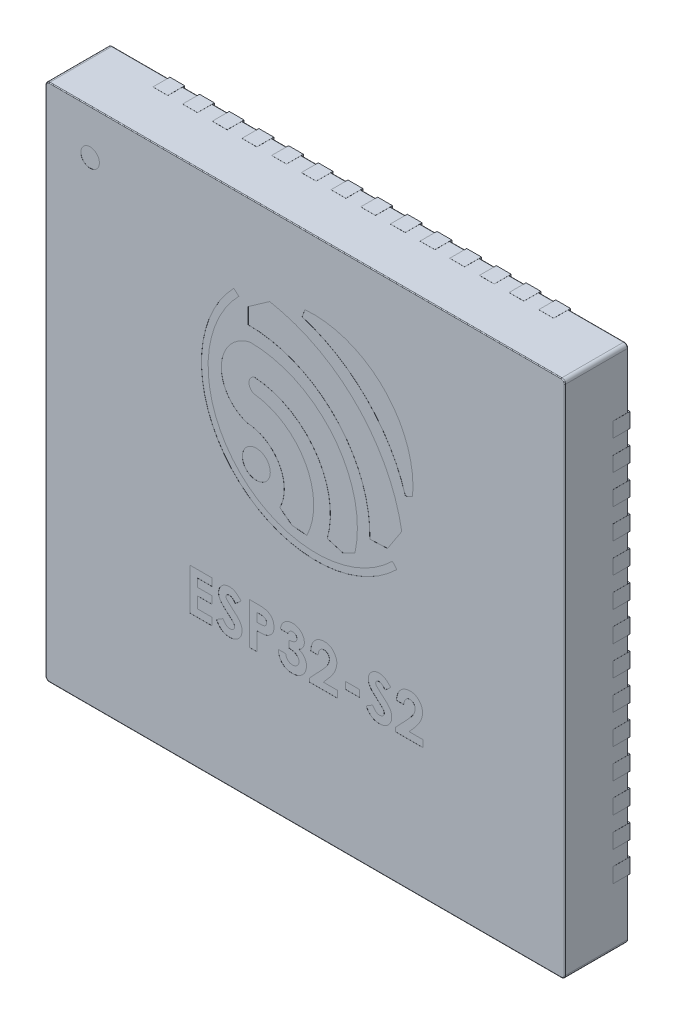
SolidWorks part; units mm, degrees
other "ESP32-S2-SoC" parameters "D5"=0.3678, "D1"=3.1308, "D2"=3.0402, "D3"=0.4115, "D4"=0.3, "D6"=0.3296, "D7"=0.2637, "D8"=0.9806, "D10"=0.4, "D11"=0.25, "D9"=7
ref_plane "Front Plane" through (0, 0, 0) normal (0, 0, 1) x (1, 0, 0)
ref_plane "Top Plane" through (0, 0, 0) normal (0, 1, 0) x (1, 0, 0)
ref_plane "Right Plane" through (0, 0, 0) normal (1, 0, 0) x (0, 0, -1)
sketch "Sketch1" plane through (0, 0, 0) normal (0, 1, 0) x (1, 0, 0)
  line L1 (-3.5, -3.5) -> (3.5, -3.5)
  line L2 (-3.5, -3.5) -> (-3.5, 3.5)
  line L3 (-3.5, 3.5) -> (3.5, 3.5)
  line L4 (3.5, -3.5) -> (3.5, 3.5)
  line L5 (-3.5, -3.5) -> (3.5, 3.5) construction
  line L6 (-3.5, 3.5) -> (3.5, -3.5) construction
  point P0 (0, 0)
  dimension "D1" = 7
  dimension "D2" = 7
extrude "Boss-Extrude1" add sketch "Sketch1" along normal blind 0.85
fillet "Fillet1" radius 0.05 4 edges at (3.5, 0.425, -3.5) (3.5, 0.425, 3.5) (-3.5, 0.425, 3.5) (-3.5, 0.425, -3.5)
fillet "Fillet2" radius 0.01 16 edges at (3.4854, 0.85, 3.4854) (0, 0.85, 3.5) (-3.4854, 0.85, 3.4854) (-3.5, 0.85, 0) (-3.4854, 0.85, -3.4854) (0, 0.85, -3.5) (3.4854, 0.85, -3.4854) (3.5, 0.85, 0) (3.5, 0, 0) (3.4854, 0, -3.4854) (0, 0, -3.5) (3.4854, 0, 3.4854) (0, 0, 3.5) (-3.4854, 0, 3.4854) (-3.5, 0, 0) (-3.4854, 0, -3.4854)
sketch "Sketch2" plane through (0, 0, 0) normal (0, -1, 0) x (1, 0, 0)
  line L0 (1.5, 2) -> (2, 1.5)
  line L1 (-1.875, -2) -> (1.875, -2)
  line L2 (-2, -1.875) -> (-2, 1.875)
  line L3 (-1.875, 2) -> (1.5, 2)
  line L4 (2, -1.875) -> (2, 1.5)
  line L5 (-1.9634, -1.9634) -> (2, 2) construction
  line L6 (-1.9634, 1.9634) -> (1.9634, -1.9634) construction
  line L7 (1.5, 2) -> (2, 2) construction
  line L8 (2, 1.5) -> (2, 2) construction
  line L9 (-2, 2) -> (-1.875, 2) construction
  line L10 (-2, 2) -> (-1.9634, 1.9634) construction
  line L11 (-2, 1.875) -> (-2, 2) construction
  line L12 (-2, -2) -> (-2, -1.875) construction
  line L13 (-2, -2) -> (-1.9634, -1.9634) construction
  line L14 (-2, -2) -> (-1.875, -2) construction
  line L15 (2, -2) -> (2, -1.875) construction
  line L16 (1.9634, -1.9634) -> (2, -2) construction
  line L17 (1.875, -2) -> (2, -2) construction
  line L18 (-1.9, 3.501) -> (-1.9, 3.101)
  line L23 (-0.3, 3.501) -> (-0.1, 3.501)
  line L24 (-0.3, 3.501) -> (-0.3, 3.101)
  line L25 (-0.3, 3.101) -> (-0.1, 3.101)
  line L26 (-0.1, 3.501) -> (-0.1, 3.101)
  line L27 (-0.3, 3.501) -> (-0.1, 3.101) construction
  line L28 (-0.3, 3.101) -> (-0.1, 3.501) construction
  line L30 (-0.7, 3.501) -> (-0.7, 3.101)
  line L31 (-0.7, 3.501) -> (-0.5, 3.501)
  line L32 (-0.5, 3.501) -> (-0.5, 3.101)
  line L33 (-0.7, 3.101) -> (-0.5, 3.101)
  line L34 (-0.7, 3.101) -> (-0.5, 3.501) construction
  line L35 (-0.7, 3.501) -> (-0.5, 3.101) construction
  line L36 (-1.1, 3.501) -> (-1.1, 3.101)
  line L37 (-1.1, 3.501) -> (-0.9, 3.501)
  line L38 (-0.9, 3.501) -> (-0.9, 3.101)
  line L39 (-1.1, 3.101) -> (-0.9, 3.101)
  line L40 (-1.1, 3.101) -> (-0.9, 3.501) construction
  line L41 (-1.1, 3.501) -> (-0.9, 3.101) construction
  line L42 (-1.5, 3.501) -> (-1.5, 3.101)
  line L43 (-1.5, 3.501) -> (-1.3, 3.501)
  line L44 (-1.3, 3.501) -> (-1.3, 3.101)
  line L45 (-1.5, 3.101) -> (-1.3, 3.101)
  line L46 (-1.5, 3.101) -> (-1.3, 3.501) construction
  line L47 (-1.5, 3.501) -> (-1.3, 3.101) construction
  line L48 (-0.3, 3.501) -> (-0.7, 3.501) construction
  line L49 (0, 0.0183) -> (0, 4.8642) construction
  line L66 (0, -1000) -> (0, 49000) construction
  line L162 (-1.9, 3.501) -> (-1.7, 3.501)
  line L163 (-3.5, 3.5) -> (3.5, 3.5) construction
  line L164 (-1.7, 3.501) -> (-1.7, 3.101)
  line L165 (-1.9, 3.101) -> (-1.7, 3.101)
  line L166 (-1.9, 3.101) -> (-1.7, 3.501) construction
  line L167 (-1.9, 3.501) -> (-1.7, 3.101) construction
  line L168 (-2.3, 3.501) -> (-2.3, 3.101)
  line L169 (-2.3, 3.501) -> (-2.1, 3.501)
  line L170 (-2.1, 3.501) -> (-2.1, 3.101)
  line L171 (-2.3, 3.101) -> (-2.1, 3.101)
  line L172 (-2.3, 3.101) -> (-2.1, 3.501) construction
  line L173 (-2.3, 3.501) -> (-2.1, 3.101) construction
  line L174 (-2.7, 3.501) -> (-2.7, 3.101)
  line L175 (-2.7, 3.501) -> (-2.5, 3.501)
  line L176 (-2.5, 3.501) -> (-2.5, 3.101)
  line L177 (-2.7, 3.101) -> (-2.5, 3.101)
  line L178 (-2.7, 3.101) -> (-2.5, 3.501) construction
  line L179 (-2.7, 3.501) -> (-2.5, 3.101) construction
  line L180 (-1000, 0) -> (49000, 0) construction
  line L181 (2.7, 3.501) -> (2.5, 3.101) construction
  line L182 (2.7, 3.101) -> (2.5, 3.501) construction
  line L183 (2.3, 3.501) -> (2.1, 3.101) construction
  line L184 (2.3, 3.101) -> (2.1, 3.501) construction
  line L185 (1.9, 3.501) -> (1.7, 3.101) construction
  line L186 (1.9, 3.101) -> (1.7, 3.501) construction
  line L187 (0.3, 3.501) -> (0.7, 3.501) construction
  line L188 (1.5, 3.501) -> (1.3, 3.101) construction
  line L189 (1.5, 3.101) -> (1.3, 3.501) construction
  line L190 (1.1, 3.501) -> (0.9, 3.101) construction
  line L191 (1.1, 3.101) -> (0.9, 3.501) construction
  line L192 (0.7, 3.501) -> (0.5, 3.101) construction
  line L193 (0.7, 3.101) -> (0.5, 3.501) construction
  line L194 (0.3, 3.101) -> (0.1, 3.501) construction
  line L195 (0.3, 3.501) -> (0.1, 3.101) construction
  line L196 (2.7, 3.101) -> (2.5, 3.101)
  line L197 (2.5, 3.501) -> (2.5, 3.101)
  line L198 (2.7, 3.501) -> (2.5, 3.501)
  line L199 (2.7, 3.501) -> (2.7, 3.101)
  line L200 (2.3, 3.101) -> (2.1, 3.101)
  line L201 (2.1, 3.501) -> (2.1, 3.101)
  line L202 (2.3, 3.501) -> (2.1, 3.501)
  line L203 (2.3, 3.501) -> (2.3, 3.101)
  line L204 (1.9, 3.101) -> (1.7, 3.101)
  line L205 (1.7, 3.501) -> (1.7, 3.101)
  line L206 (1.9, 3.501) -> (1.7, 3.501)
  line L207 (1.5, 3.101) -> (1.3, 3.101)
  line L208 (1.3, 3.501) -> (1.3, 3.101)
  line L209 (1.5, 3.501) -> (1.3, 3.501)
  line L210 (1.5, 3.501) -> (1.5, 3.101)
  line L211 (1.1, 3.101) -> (0.9, 3.101)
  line L212 (0.9, 3.501) -> (0.9, 3.101)
  line L213 (1.1, 3.501) -> (0.9, 3.501)
  line L214 (1.1, 3.501) -> (1.1, 3.101)
  line L215 (0.7, 3.101) -> (0.5, 3.101)
  line L216 (0.5, 3.501) -> (0.5, 3.101)
  line L217 (0.7, 3.501) -> (0.5, 3.501)
  line L218 (0.7, 3.501) -> (0.7, 3.101)
  line L219 (0.1, 3.501) -> (0.1, 3.101)
  line L220 (0.3, 3.101) -> (0.1, 3.101)
  line L221 (0.3, 3.501) -> (0.3, 3.101)
  line L222 (0.3, 3.501) -> (0.1, 3.501)
  line L223 (1.9, 3.501) -> (1.9, 3.101)
  line L224 (0.3, -3.501) -> (0.1, -3.101) construction
  line L225 (0.3, -3.101) -> (0.1, -3.501) construction
  line L226 (0.7, -3.101) -> (0.5, -3.501) construction
  line L227 (0.7, -3.501) -> (0.5, -3.101) construction
  line L228 (1.1, -3.101) -> (0.9, -3.501) construction
  line L229 (1.1, -3.501) -> (0.9, -3.101) construction
  line L230 (1.5, -3.101) -> (1.3, -3.501) construction
  line L231 (1.5, -3.501) -> (1.3, -3.101) construction
  line L232 (0.3, -3.501) -> (0.7, -3.501) construction
  line L233 (1.9, -3.101) -> (1.7, -3.501) construction
  line L234 (1.9, -3.501) -> (1.7, -3.101) construction
  line L235 (2.3, -3.101) -> (2.1, -3.501) construction
  line L236 (2.3, -3.501) -> (2.1, -3.101) construction
  line L237 (2.7, -3.101) -> (2.5, -3.501) construction
  line L238 (2.7, -3.501) -> (2.5, -3.101) construction
  line L239 (-2.7, -3.501) -> (-2.5, -3.101) construction
  line L240 (-2.7, -3.101) -> (-2.5, -3.501) construction
  line L241 (-2.3, -3.501) -> (-2.1, -3.101) construction
  line L242 (-2.3, -3.101) -> (-2.1, -3.501) construction
  line L243 (-1.9, -3.501) -> (-1.7, -3.101) construction
  line L244 (-1.9, -3.101) -> (-1.7, -3.501) construction
  line L245 (-0.3, -3.501) -> (-0.7, -3.501) construction
  line L246 (-1.5, -3.501) -> (-1.3, -3.101) construction
  line L247 (-1.5, -3.101) -> (-1.3, -3.501) construction
  line L248 (-1.1, -3.501) -> (-0.9, -3.101) construction
  line L249 (-1.1, -3.101) -> (-0.9, -3.501) construction
  line L250 (-0.7, -3.501) -> (-0.5, -3.101) construction
  line L251 (-0.7, -3.101) -> (-0.5, -3.501) construction
  line L252 (-0.3, -3.101) -> (-0.1, -3.501) construction
  line L253 (-0.3, -3.501) -> (-0.1, -3.101) construction
  line L254 (1.9, -3.501) -> (1.9, -3.101)
  line L255 (0.3, -3.501) -> (0.1, -3.501)
  line L256 (0.3, -3.501) -> (0.3, -3.101)
  line L257 (0.3, -3.101) -> (0.1, -3.101)
  line L258 (0.1, -3.501) -> (0.1, -3.101)
  line L259 (0.7, -3.501) -> (0.7, -3.101)
  line L260 (0.7, -3.501) -> (0.5, -3.501)
  line L261 (0.5, -3.501) -> (0.5, -3.101)
  line L262 (0.7, -3.101) -> (0.5, -3.101)
  line L263 (1.1, -3.501) -> (1.1, -3.101)
  line L264 (1.1, -3.501) -> (0.9, -3.501)
  line L265 (0.9, -3.501) -> (0.9, -3.101)
  line L266 (1.1, -3.101) -> (0.9, -3.101)
  line L267 (1.5, -3.501) -> (1.5, -3.101)
  line L268 (1.5, -3.501) -> (1.3, -3.501)
  line L269 (1.3, -3.501) -> (1.3, -3.101)
  line L270 (1.5, -3.101) -> (1.3, -3.101)
  line L271 (1.9, -3.501) -> (1.7, -3.501)
  line L272 (1.7, -3.501) -> (1.7, -3.101)
  line L273 (1.9, -3.101) -> (1.7, -3.101)
  line L274 (2.3, -3.501) -> (2.3, -3.101)
  line L275 (2.3, -3.501) -> (2.1, -3.501)
  line L276 (2.1, -3.501) -> (2.1, -3.101)
  line L277 (2.3, -3.101) -> (2.1, -3.101)
  line L278 (2.7, -3.501) -> (2.7, -3.101)
  line L279 (2.7, -3.501) -> (2.5, -3.501)
  line L280 (2.5, -3.501) -> (2.5, -3.101)
  line L281 (2.7, -3.101) -> (2.5, -3.101)
  line L282 (-2.7, -3.101) -> (-2.5, -3.101)
  line L283 (-2.5, -3.501) -> (-2.5, -3.101)
  line L284 (-2.7, -3.501) -> (-2.5, -3.501)
  line L285 (-2.7, -3.501) -> (-2.7, -3.101)
  line L286 (-2.3, -3.101) -> (-2.1, -3.101)
  line L287 (-2.1, -3.501) -> (-2.1, -3.101)
  line L288 (-2.3, -3.501) -> (-2.1, -3.501)
  line L289 (-2.3, -3.501) -> (-2.3, -3.101)
  line L290 (-1.9, -3.101) -> (-1.7, -3.101)
  line L291 (-1.7, -3.501) -> (-1.7, -3.101)
  line L292 (-1.9, -3.501) -> (-1.7, -3.501)
  line L293 (-1.5, -3.101) -> (-1.3, -3.101)
  line L294 (-1.3, -3.501) -> (-1.3, -3.101)
  line L295 (-1.5, -3.501) -> (-1.3, -3.501)
  line L296 (-1.5, -3.501) -> (-1.5, -3.101)
  line L297 (-1.1, -3.101) -> (-0.9, -3.101)
  line L298 (-0.9, -3.501) -> (-0.9, -3.101)
  line L299 (-1.1, -3.501) -> (-0.9, -3.501)
  line L300 (-1.1, -3.501) -> (-1.1, -3.101)
  line L301 (-0.7, -3.101) -> (-0.5, -3.101)
  line L302 (-0.5, -3.501) -> (-0.5, -3.101)
  line L303 (-0.7, -3.501) -> (-0.5, -3.501)
  line L304 (-0.7, -3.501) -> (-0.7, -3.101)
  line L305 (-0.1, -3.501) -> (-0.1, -3.101)
  line L306 (-0.3, -3.101) -> (-0.1, -3.101)
  line L307 (-0.3, -3.501) -> (-0.3, -3.101)
  line L308 (-0.3, -3.501) -> (-0.1, -3.501)
  line L309 (-1.9, -3.501) -> (-1.9, -3.101)
  line L310 (3.501, 0.3) -> (3.101, 0.1) construction
  line L311 (3.101, 0.3) -> (3.501, 0.1) construction
  line L312 (3.101, 0.7) -> (3.501, 0.5) construction
  line L313 (3.501, 0.7) -> (3.101, 0.5) construction
  line L314 (3.101, 1.1) -> (3.501, 0.9) construction
  line L315 (3.501, 1.1) -> (3.101, 0.9) construction
  line L316 (3.101, 1.5) -> (3.501, 1.3) construction
  line L317 (3.501, 1.5) -> (3.101, 1.3) construction
  line L318 (3.501, 0.3) -> (3.501, 0.7) construction
  line L319 (3.101, 1.9) -> (3.501, 1.7) construction
  line L320 (3.501, 1.9) -> (3.101, 1.7) construction
  line L321 (3.101, 2.3) -> (3.501, 2.1) construction
  line L322 (3.501, 2.3) -> (3.101, 2.1) construction
  line L323 (3.101, 2.7) -> (3.501, 2.5) construction
  line L324 (3.501, 2.7) -> (3.101, 2.5) construction
  line L325 (3.501, -2.7) -> (3.101, -2.5) construction
  line L326 (3.101, -2.7) -> (3.501, -2.5) construction
  line L327 (3.501, -2.3) -> (3.101, -2.1) construction
  line L328 (3.101, -2.3) -> (3.501, -2.1) construction
  line L329 (3.501, -1.9) -> (3.101, -1.7) construction
  line L330 (3.101, -1.9) -> (3.501, -1.7) construction
  line L331 (3.501, -0.3) -> (3.501, -0.7) construction
  line L332 (3.501, -1.5) -> (3.101, -1.3) construction
  line L333 (3.101, -1.5) -> (3.501, -1.3) construction
  line L334 (3.501, -1.1) -> (3.101, -0.9) construction
  line L335 (3.101, -1.1) -> (3.501, -0.9) construction
  line L336 (3.501, -0.7) -> (3.101, -0.5) construction
  line L337 (3.101, -0.7) -> (3.501, -0.5) construction
  line L338 (3.101, -0.3) -> (3.501, -0.1) construction
  line L339 (3.501, -0.3) -> (3.101, -0.1) construction
  line L340 (3.501, 1.9) -> (3.101, 1.9)
  line L341 (3.501, 0.3) -> (3.501, 0.1)
  line L342 (3.501, 0.3) -> (3.101, 0.3)
  line L343 (3.101, 0.3) -> (3.101, 0.1)
  line L344 (3.501, 0.1) -> (3.101, 0.1)
  line L345 (3.501, 0.7) -> (3.101, 0.7)
  line L346 (3.501, 0.7) -> (3.501, 0.5)
  line L347 (3.501, 0.5) -> (3.101, 0.5)
  line L348 (3.101, 0.7) -> (3.101, 0.5)
  line L349 (3.501, 1.1) -> (3.101, 1.1)
  line L350 (3.501, 1.1) -> (3.501, 0.9)
  line L351 (3.501, 0.9) -> (3.101, 0.9)
  line L352 (3.101, 1.1) -> (3.101, 0.9)
  line L353 (3.501, 1.5) -> (3.101, 1.5)
  line L354 (3.501, 1.5) -> (3.501, 1.3)
  line L355 (3.501, 1.3) -> (3.101, 1.3)
  line L356 (3.101, 1.5) -> (3.101, 1.3)
  line L357 (3.501, 1.9) -> (3.501, 1.7)
  line L358 (3.501, 1.7) -> (3.101, 1.7)
  line L359 (3.101, 1.9) -> (3.101, 1.7)
  line L360 (3.501, 2.3) -> (3.101, 2.3)
  line L361 (3.501, 2.3) -> (3.501, 2.1)
  line L362 (3.501, 2.1) -> (3.101, 2.1)
  line L363 (3.101, 2.3) -> (3.101, 2.1)
  line L364 (3.501, 2.7) -> (3.101, 2.7)
  line L365 (3.501, 2.7) -> (3.501, 2.5)
  line L366 (3.501, 2.5) -> (3.101, 2.5)
  line L367 (3.101, 2.7) -> (3.101, 2.5)
  line L368 (3.101, -2.7) -> (3.101, -2.5)
  line L369 (3.501, -2.5) -> (3.101, -2.5)
  line L370 (3.501, -2.7) -> (3.501, -2.5)
  line L371 (3.501, -2.7) -> (3.101, -2.7)
  line L372 (3.101, -2.3) -> (3.101, -2.1)
  line L373 (3.501, -2.1) -> (3.101, -2.1)
  line L374 (3.501, -2.3) -> (3.501, -2.1)
  line L375 (3.501, -2.3) -> (3.101, -2.3)
  line L376 (3.101, -1.9) -> (3.101, -1.7)
  line L377 (3.501, -1.7) -> (3.101, -1.7)
  line L378 (3.501, -1.9) -> (3.501, -1.7)
  line L379 (3.101, -1.5) -> (3.101, -1.3)
  line L380 (3.501, -1.3) -> (3.101, -1.3)
  line L381 (3.501, -1.5) -> (3.501, -1.3)
  line L382 (3.501, -1.5) -> (3.101, -1.5)
  line L383 (3.101, -1.1) -> (3.101, -0.9)
  line L384 (3.501, -0.9) -> (3.101, -0.9)
  line L385 (3.501, -1.1) -> (3.501, -0.9)
  line L386 (3.501, -1.1) -> (3.101, -1.1)
  line L387 (3.101, -0.7) -> (3.101, -0.5)
  line L388 (3.501, -0.5) -> (3.101, -0.5)
  line L389 (3.501, -0.7) -> (3.501, -0.5)
  line L390 (3.501, -0.7) -> (3.101, -0.7)
  line L391 (3.501, -0.1) -> (3.101, -0.1)
  line L392 (3.101, -0.3) -> (3.101, -0.1)
  line L393 (3.501, -0.3) -> (3.101, -0.3)
  line L394 (3.501, -0.3) -> (3.501, -0.1)
  line L395 (3.501, -1.9) -> (3.101, -1.9)
  line L396 (-3.501, -0.3) -> (-3.101, -0.1) construction
  line L397 (-3.101, -0.3) -> (-3.501, -0.1) construction
  line L398 (-3.101, -0.7) -> (-3.501, -0.5) construction
  line L399 (-3.501, -0.7) -> (-3.101, -0.5) construction
  line L400 (-3.101, -1.1) -> (-3.501, -0.9) construction
  line L401 (-3.501, -1.1) -> (-3.101, -0.9) construction
  line L402 (-3.101, -1.5) -> (-3.501, -1.3) construction
  line L403 (-3.501, -1.5) -> (-3.101, -1.3) construction
  line L404 (-3.501, -0.3) -> (-3.501, -0.7) construction
  line L405 (-3.101, -1.9) -> (-3.501, -1.7) construction
  line L406 (-3.501, -1.9) -> (-3.101, -1.7) construction
  line L407 (-3.101, -2.3) -> (-3.501, -2.1) construction
  line L408 (-3.501, -2.3) -> (-3.101, -2.1) construction
  line L409 (-3.101, -2.7) -> (-3.501, -2.5) construction
  line L410 (-3.501, -2.7) -> (-3.101, -2.5) construction
  line L411 (-3.501, 2.7) -> (-3.101, 2.5) construction
  line L412 (-3.101, 2.7) -> (-3.501, 2.5) construction
  line L413 (-3.501, 2.3) -> (-3.101, 2.1) construction
  line L414 (-3.101, 2.3) -> (-3.501, 2.1) construction
  line L415 (-3.501, 1.9) -> (-3.101, 1.7) construction
  line L416 (-3.101, 1.9) -> (-3.501, 1.7) construction
  line L417 (-3.501, 0.3) -> (-3.501, 0.7) construction
  line L418 (-3.501, 1.5) -> (-3.101, 1.3) construction
  line L419 (-3.101, 1.5) -> (-3.501, 1.3) construction
  line L420 (-3.501, 1.1) -> (-3.101, 0.9) construction
  line L421 (-3.101, 1.1) -> (-3.501, 0.9) construction
  line L422 (-3.501, 0.7) -> (-3.101, 0.5) construction
  line L423 (-3.101, 0.7) -> (-3.501, 0.5) construction
  line L424 (-3.101, 0.3) -> (-3.501, 0.1) construction
  line L425 (-3.501, 0.3) -> (-3.101, 0.1) construction
  line L426 (-3.501, -1.9) -> (-3.101, -1.9)
  line L427 (-3.501, -0.3) -> (-3.501, -0.1)
  line L428 (-3.501, -0.3) -> (-3.101, -0.3)
  line L429 (-3.101, -0.3) -> (-3.101, -0.1)
  line L430 (-3.501, -0.1) -> (-3.101, -0.1)
  line L431 (-3.501, -0.7) -> (-3.101, -0.7)
  line L432 (-3.501, -0.7) -> (-3.501, -0.5)
  line L433 (-3.501, -0.5) -> (-3.101, -0.5)
  line L434 (-3.101, -0.7) -> (-3.101, -0.5)
  line L435 (-3.501, -1.1) -> (-3.101, -1.1)
  line L436 (-3.501, -1.1) -> (-3.501, -0.9)
  line L437 (-3.501, -0.9) -> (-3.101, -0.9)
  line L438 (-3.101, -1.1) -> (-3.101, -0.9)
  line L439 (-3.501, -1.5) -> (-3.101, -1.5)
  line L440 (-3.501, -1.5) -> (-3.501, -1.3)
  line L441 (-3.501, -1.3) -> (-3.101, -1.3)
  line L442 (-3.101, -1.5) -> (-3.101, -1.3)
  line L443 (-3.501, -1.9) -> (-3.501, -1.7)
  line L444 (-3.501, -1.7) -> (-3.101, -1.7)
  line L445 (-3.101, -1.9) -> (-3.101, -1.7)
  line L446 (-3.501, -2.3) -> (-3.101, -2.3)
  line L447 (-3.501, -2.3) -> (-3.501, -2.1)
  line L448 (-3.501, -2.1) -> (-3.101, -2.1)
  line L449 (-3.101, -2.3) -> (-3.101, -2.1)
  line L450 (-3.501, -2.7) -> (-3.101, -2.7)
  line L451 (-3.501, -2.7) -> (-3.501, -2.5)
  line L452 (-3.501, -2.5) -> (-3.101, -2.5)
  line L453 (-3.101, -2.7) -> (-3.101, -2.5)
  line L454 (-3.101, 2.7) -> (-3.101, 2.5)
  line L455 (-3.501, 2.5) -> (-3.101, 2.5)
  line L456 (-3.501, 2.7) -> (-3.501, 2.5)
  line L457 (-3.501, 2.7) -> (-3.101, 2.7)
  line L458 (-3.101, 2.3) -> (-3.101, 2.1)
  line L459 (-3.501, 2.1) -> (-3.101, 2.1)
  line L460 (-3.501, 2.3) -> (-3.501, 2.1)
  line L461 (-3.501, 2.3) -> (-3.101, 2.3)
  line L462 (-3.101, 1.9) -> (-3.101, 1.7)
  line L463 (-3.501, 1.7) -> (-3.101, 1.7)
  line L464 (-3.501, 1.9) -> (-3.501, 1.7)
  line L465 (-3.101, 1.5) -> (-3.101, 1.3)
  line L466 (-3.501, 1.3) -> (-3.101, 1.3)
  line L467 (-3.501, 1.5) -> (-3.501, 1.3)
  line L468 (-3.501, 1.5) -> (-3.101, 1.5)
  line L469 (-3.101, 1.1) -> (-3.101, 0.9)
  line L470 (-3.501, 0.9) -> (-3.101, 0.9)
  line L471 (-3.501, 1.1) -> (-3.501, 0.9)
  line L472 (-3.501, 1.1) -> (-3.101, 1.1)
  line L473 (-3.101, 0.7) -> (-3.101, 0.5)
  line L474 (-3.501, 0.5) -> (-3.101, 0.5)
  line L475 (-3.501, 0.7) -> (-3.501, 0.5)
  line L476 (-3.501, 0.7) -> (-3.101, 0.7)
  line L477 (-3.501, 0.1) -> (-3.101, 0.1)
  line L478 (-3.101, 0.3) -> (-3.101, 0.1)
  line L479 (-3.501, 0.3) -> (-3.101, 0.3)
  line L480 (-3.501, 0.3) -> (-3.501, 0.1)
  line L481 (-3.501, 1.9) -> (-3.101, 1.9)
  arc A0 (-1.875, 2) -> (-2, 1.875) centre (-1.875, 1.875) ccw
  arc A1 (-2, -1.875) -> (-1.875, -2) centre (-1.875, -1.875) ccw
  arc A2 (1.875, -2) -> (2, -1.875) centre (1.875, -1.875) ccw
  point P0 (0, 0)
  point P12 (-0.2, 3.301)
  point P76 (0.2, 3.301)
  point P133 (0.2, -3.301)
  point P134 (-0.2, -3.301)
  point P201 (3.301, 0.2)
  point P202 (3.301, -0.2)
  point P259 (-3.301, -0.2)
  point P260 (-3.301, 0.2)
  dimension "D5" = 0.25
  dimension "D1" = 4
  dimension "D2" = 4
  dimension "D4" = 45
  dimension "D7" = 0.2
  dimension "D8" = 0.2
  dimension "D11" = 0.001
  dimension "D6" = 0.4
  dimension "D3" = 0.5
extrude "Boss-Extrude2" add sketch "Sketch2" along normal blind 0.025 and the other way blind 0.203
sketch "Sketch3" plane through (0, 0.85, 0) normal (0, 1, 0) x (1, 0, 0)
  line L7 (-3.5, 1.745) -> (3.49, 1.745) construction
  line L8 (-3.5, 3.5) -> (-3.5, -3.5) construction
  line L9 (3.5, 3.45) -> (3.5, -3.45) construction
  line L11 (3.49, -3.45) -> (3.49, 3.45) construction
  line L12 (3.45, -3.5) -> (-3.45, -3.5) construction
  line L13 (-1.3495, -1.0723) -> (-1.4462, -1.1135)
  line L14 (0.005, -2.5722) -> (0.0419, -2.4695)
  line L15 (-0.8695, -0.3305) -> (-1.1077, -0.3407)
  line L16 (-1.1077, -0.3407) -> (-1.3002, -0.6346)
  line L17 (0.4805, -2.4287) -> (0.7694, -2.2259)
  line L18 (0.7694, -2.2259) -> (0.7694, -2.0129)
  line L19 (0.896, -2.2826) -> (0.9633, -2.3422)
  line L20 (-1.2346, -0.158) -> (-1.1747, -0.2251)
  line L21 (0.3438, -0.0924) -> (0.178, 0.033)
  line L22 (0.178, 0.033) -> (-0.021, 0.0506)
  line L23 (-0.2956, -0.051) -> (-0.506, 0.0116)
  line L24 (-0.506, 0.0116) -> (-0.6698, -0.0704)
  line L25 (0, 0) -> (0, 3.49) construction
  line L26 (3.45, 3.49) -> (-3.45, 3.49) construction
  circle A10 centre (2.9, -2.9) radius 0.125
  arc A11 (-1.3495, -1.0723) -> (0.0419, -2.4695) centre (0.66, -0.4626) ccw
  arc A12 (-1.3002, -0.6346) -> (0.4805, -2.4287) centre (0.8726, -0.2588) ccw
  arc A13 (0.7453, -1.8229) -> (0.7866, -0.8611) centre (0.6326, -1.3363) ccw
  arc A14 (0.9633, -2.3422) -> (-1.2346, -0.158) centre (-0.1498, -1.2644) ccw
  circle A15 centre (0.66, -0.4394) radius 0.1881
  arc A16 (-0.2956, -0.051) -> (0.685, -1.4427) centre (0.7544, -0.3525) ccw
  arc A17 (0.3438, -0.0924) -> (0.7866, -0.8611) centre (0.809, -0.3363) ccw
  arc A18 (-0.021, 0.0506) -> (0.6887, -1.2452) centre (0.7889, -0.3481) ccw
  arc A19 (-0.6698, -0.0704) -> (0.7453, -1.8229) centre (0.7458, -0.3749) ccw
  arc A20 (0.896, -2.2826) -> (-1.1747, -0.2251) centre (-0.1498, -1.2644) ccw
  arc A21 (-0.8695, -0.3305) -> (0.7694, -2.0129) centre (0.7678, -0.375) ccw
  arc A22 (0.6887, -1.2452) -> (0.685, -1.4427) centre (0.6555, -1.3434) cw
  arc A23 (-1.4462, -1.1135) -> (0.005, -2.5722) centre (-0.1063, -1.2317) ccw
  text T0 "ESP32-S2" font "Century Gothic" height 0.56
  point P0 (0, 1.745)
  point P54 (0, 0)
  dimension "D2" = 0.25
  dimension "D3" = 0.6
  dimension "D4" = 0.6
extrude "Cut-Extrude1" cut sketch "Sketch3" against normal blind 0.001
move or copy body "Body-Move/Copy1" bodies to move or copy 131 copy no rotation origin (0, 0, 0) rotation axis (0, 0.7071, 0.7071) rotation angle 180
move or copy body "Body-Move/Copy2" bodies to move or copy 132 copy no translate (0, 0, 0.025)
equation "\"D8@Sketch2\"=\"D10@Sketch2\"/2"
equation "\"D4@Sketch3\"=\"D3@Sketch3\""
